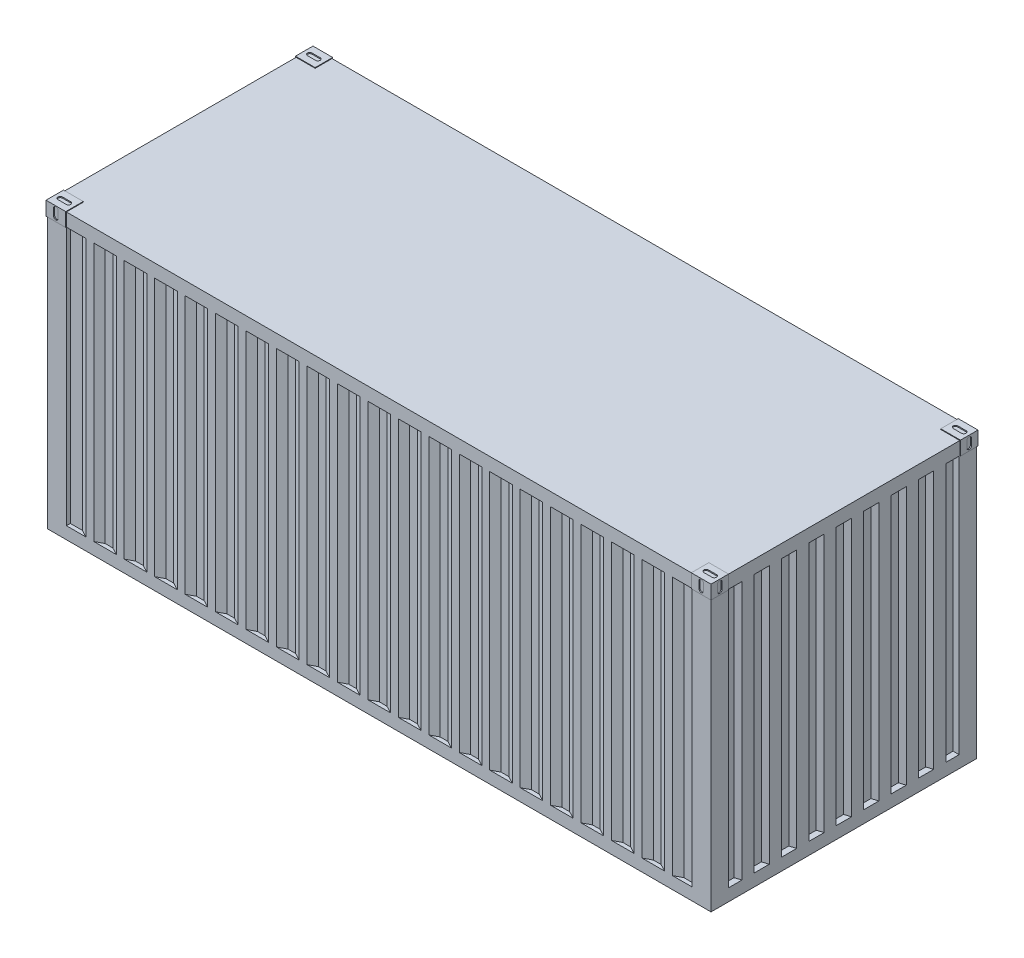
SolidWorks part; units mm, degrees
ref_plane "Front Plane" through (0, 0, 0) normal (0, 0, 1) x (1, 0, 0)
ref_plane "Top Plane" through (0, 0, 0) normal (0, 1, 0) x (1, 0, 0)
ref_plane "Right Plane" through (0, 0, 0) normal (1, 0, 0) x (0, 0, -1)
sketch "Sketch1" plane through (0, 0, 0) normal (0, 1, 0) x (1, 0, 0)
  line L1 (0, 0) -> (6058, 0)
  line L2 (0, 0) -> (0, 2424.7)
  line L3 (0, 2424.7) -> (6058, 2424.7)
  line L4 (6058, 0) -> (6058, 2424.7)
  dimension "D1" = 6058
  dimension "D2" = 2424.7
extrude "Boss-Extrude1" add sketch "Sketch1" along normal blind 2591
ref_plane "Plane-Mid-Length" through (0, 0, -1212.35) normal (0, 0, 1) x (1, 0, 0)
ref_plane "Plane-Mid-Width" through (3029, 0, 0) normal (-1, 0, 0) x (0, 0, 1)
ref_plane "Plane-Mid-Height" through (0, 1295.5, 0) normal (0, 1, 0) x (1, 0, 0)
ref_plane "Top of Corrugation" through (0, 2471, 0) normal (0, 1, 0) x (1, 0, 0)
ref_plane "Floor/Bottom of Corrugation" through (0, 111, 0) normal (0, 1, 0) x (1, 0, 0)
sketch "Sketch4" plane through (0, 2591, 0) normal (0, 1, 0) x (1, 0, 0)
  line L0 (6058, 2424.7) -> (5884, 2424.7)
  line L1 (6058, 2424.7) -> (0, 2424.7) construction
  line L2 (5884, 2424.7) -> (5884, 2388.7)
  line L3 (5884, 2388.7) -> (5774, 2388.7)
  line L4 (5774, 2388.7) -> (5706, 2424.7)
  line L5 (5706, 2424.7) -> (5634, 2424.7)
  line L6 (5634, 2424.7) -> (5566, 2388.7)
  line L7 (5566, 2388.7) -> (5496, 2388.7)
  line L8 (5496, 2388.7) -> (5428, 2424.7)
  line L9 (5428, 2424.7) -> (5356, 2424.7)
  line L10 (5356, 2424.7) -> (5288, 2388.7)
  line L11 (5288, 2388.7) -> (5218, 2388.7)
  line L12 (5218, 2388.7) -> (5150, 2424.7)
  line L13 (5150, 2424.7) -> (5078, 2424.7)
  line L14 (5078, 2424.7) -> (5010, 2388.7)
  line L15 (5010, 2388.7) -> (4940, 2388.7)
  line L16 (4940, 2388.7) -> (4872, 2424.7)
  line L17 (4872, 2424.7) -> (4800, 2424.7)
  line L18 (4800, 2424.7) -> (4732, 2388.7)
  line L19 (4732, 2388.7) -> (4662, 2388.7)
  line L20 (4662, 2388.7) -> (4594, 2424.7)
  line L21 (4594, 2424.7) -> (4522, 2424.7)
  line L22 (4522, 2424.7) -> (4454, 2388.7)
  line L23 (4454, 2388.7) -> (4384, 2388.7)
  line L24 (4384, 2388.7) -> (4316, 2424.7)
  line L25 (4316, 2424.7) -> (4244, 2424.7)
  line L26 (4244, 2424.7) -> (4176, 2388.7)
  line L27 (4176, 2388.7) -> (4106, 2388.7)
  line L28 (4106, 2388.7) -> (4038, 2424.7)
  line L29 (4038, 2424.7) -> (3966, 2424.7)
  line L30 (3966, 2424.7) -> (3898, 2388.7)
  line L31 (3898, 2388.7) -> (3828, 2388.7)
  line L32 (3828, 2388.7) -> (3760, 2424.7)
  line L33 (3760, 2424.7) -> (3688, 2424.7)
  line L34 (3688, 2424.7) -> (3620, 2388.7)
  line L35 (3620, 2388.7) -> (3550, 2388.7)
  line L36 (3550, 2388.7) -> (3482, 2424.7)
  line L37 (3482, 2424.7) -> (3410, 2424.7)
  line L38 (3410, 2424.7) -> (3342, 2388.7)
  line L39 (3342, 2388.7) -> (3272, 2388.7)
  line L40 (3272, 2388.7) -> (3204, 2424.7)
  line L41 (3204, 2424.7) -> (3132, 2424.7)
  line L42 (3132, 2424.7) -> (3064, 2388.7)
  line L43 (3064, 2388.7) -> (2994, 2388.7)
  line L44 (2994, 2388.7) -> (2926, 2424.7)
  line L45 (2926, 2424.7) -> (2854, 2424.7)
  line L46 (2854, 2424.7) -> (2786, 2388.7)
  line L47 (2786, 2388.7) -> (2716, 2388.7)
  line L48 (2716, 2388.7) -> (2648, 2424.7)
  line L49 (2648, 2424.7) -> (2576, 2424.7)
  line L50 (2576, 2424.7) -> (2508, 2388.7)
  line L51 (2508, 2388.7) -> (2438, 2388.7)
  line L52 (2438, 2388.7) -> (2370, 2424.7)
  line L53 (2370, 2424.7) -> (2298, 2424.7)
  line L54 (2298, 2424.7) -> (2230, 2388.7)
  line L55 (2230, 2388.7) -> (2160, 2388.7)
  line L56 (2160, 2388.7) -> (2092, 2424.7)
  line L57 (2092, 2424.7) -> (2020, 2424.7)
  line L58 (2020, 2424.7) -> (1952, 2388.7)
  line L59 (1952, 2388.7) -> (1882, 2388.7)
  line L60 (1882, 2388.7) -> (1814, 2424.7)
  line L61 (1814, 2424.7) -> (1742, 2424.7)
  line L62 (1742, 2424.7) -> (1674, 2388.7)
  line L63 (1674, 2388.7) -> (1604, 2388.7)
  line L64 (1604, 2388.7) -> (1536, 2424.7)
  line L65 (1536, 2424.7) -> (1464, 2424.7)
  line L66 (1464, 2424.7) -> (1396, 2388.7)
  line L67 (1396, 2388.7) -> (1326, 2388.7)
  line L68 (1326, 2388.7) -> (1258, 2424.7)
  line L69 (1258, 2424.7) -> (1186, 2424.7)
  line L70 (1186, 2424.7) -> (1118, 2388.7)
  line L71 (1118, 2388.7) -> (1048, 2388.7)
  line L72 (1048, 2388.7) -> (980, 2424.7)
  line L73 (980, 2424.7) -> (908, 2424.7)
  line L74 (908, 2424.7) -> (840, 2388.7)
  line L75 (840, 2388.7) -> (770, 2388.7)
  line L76 (770, 2388.7) -> (702, 2424.7)
  line L77 (702, 2424.7) -> (630, 2424.7)
  line L78 (630, 2424.7) -> (562, 2388.7)
  line L79 (562, 2388.7) -> (492, 2388.7)
  line L80 (492, 2388.7) -> (424, 2424.7)
  line L81 (0, 2424.7) -> (174, 2424.7)
  line L82 (174, 2424.7) -> (174, 2388.7)
  line L83 (174, 2388.7) -> (284, 2388.7)
  line L84 (284, 2388.7) -> (352, 2424.7)
  line L85 (352, 2424.7) -> (424, 2424.7)
  line L86 (-1425.05, 1212.35) -> (1425.05, 1212.35) construction
  line L87 (352, 0) -> (424, 0)
  line L88 (284, 36) -> (352, 0)
  line L89 (174, 36) -> (284, 36)
  line L90 (174, 0) -> (174, 36)
  line L91 (0, 0) -> (174, 0)
  line L92 (492, 36) -> (424, 0)
  line L93 (562, 36) -> (492, 36)
  line L94 (630, 0) -> (562, 36)
  line L95 (702, 0) -> (630, 0)
  line L96 (770, 36) -> (702, 0)
  line L97 (840, 36) -> (770, 36)
  line L98 (908, 0) -> (840, 36)
  line L99 (980, 0) -> (908, 0)
  line L100 (1048, 36) -> (980, 0)
  line L101 (1118, 36) -> (1048, 36)
  line L102 (1186, 0) -> (1118, 36)
  line L103 (1258, 0) -> (1186, 0)
  line L104 (1326, 36) -> (1258, 0)
  line L105 (1396, 36) -> (1326, 36)
  line L106 (1464, 0) -> (1396, 36)
  line L107 (1536, 0) -> (1464, 0)
  line L108 (1604, 36) -> (1536, 0)
  line L109 (1674, 36) -> (1604, 36)
  line L110 (1742, 0) -> (1674, 36)
  line L111 (1814, 0) -> (1742, 0)
  line L112 (1882, 36) -> (1814, 0)
  line L113 (1952, 36) -> (1882, 36)
  line L114 (2020, 0) -> (1952, 36)
  line L115 (2092, 0) -> (2020, 0)
  line L116 (2160, 36) -> (2092, 0)
  line L117 (2230, 36) -> (2160, 36)
  line L118 (2298, 0) -> (2230, 36)
  line L119 (2370, 0) -> (2298, 0)
  line L120 (2438, 36) -> (2370, 0)
  line L121 (2508, 36) -> (2438, 36)
  line L122 (2576, 0) -> (2508, 36)
  line L123 (2648, 0) -> (2576, 0)
  line L124 (2716, 36) -> (2648, 0)
  line L125 (2786, 36) -> (2716, 36)
  line L126 (2854, 0) -> (2786, 36)
  line L127 (2926, 0) -> (2854, 0)
  line L128 (2994, 36) -> (2926, 0)
  line L129 (3064, 36) -> (2994, 36)
  line L130 (3132, 0) -> (3064, 36)
  line L131 (3204, 0) -> (3132, 0)
  line L132 (3272, 36) -> (3204, 0)
  line L133 (3342, 36) -> (3272, 36)
  line L134 (3410, 0) -> (3342, 36)
  line L135 (3482, 0) -> (3410, 0)
  line L136 (3550, 36) -> (3482, 0)
  line L137 (3620, 36) -> (3550, 36)
  line L138 (3688, 0) -> (3620, 36)
  line L139 (3760, 0) -> (3688, 0)
  line L140 (3828, 36) -> (3760, 0)
  line L141 (3898, 36) -> (3828, 36)
  line L142 (3966, 0) -> (3898, 36)
  line L143 (4038, 0) -> (3966, 0)
  line L144 (4106, 36) -> (4038, 0)
  line L145 (4176, 36) -> (4106, 36)
  line L146 (4244, 0) -> (4176, 36)
  line L147 (4316, 0) -> (4244, 0)
  line L148 (4384, 36) -> (4316, 0)
  line L149 (4454, 36) -> (4384, 36)
  line L150 (4522, 0) -> (4454, 36)
  line L151 (4594, 0) -> (4522, 0)
  line L152 (4662, 36) -> (4594, 0)
  line L153 (4732, 36) -> (4662, 36)
  line L154 (4800, 0) -> (4732, 36)
  line L155 (4872, 0) -> (4800, 0)
  line L156 (4940, 36) -> (4872, 0)
  line L157 (5010, 36) -> (4940, 36)
  line L158 (5078, 0) -> (5010, 36)
  line L159 (5150, 0) -> (5078, 0)
  line L160 (5218, 36) -> (5150, 0)
  line L161 (5288, 36) -> (5218, 36)
  line L162 (5356, 0) -> (5288, 36)
  line L163 (5428, 0) -> (5356, 0)
  line L164 (5496, 36) -> (5428, 0)
  line L165 (5566, 36) -> (5496, 36)
  line L166 (5634, 0) -> (5566, 36)
  line L167 (5706, 0) -> (5634, 0)
  line L168 (5774, 36) -> (5706, 0)
  line L169 (5884, 36) -> (5774, 36)
  line L170 (5884, 0) -> (5884, 36)
  line L171 (6058, 0) -> (5884, 0)
  line L172 (6058, 2424.7) -> (6058, 2264.7)
  line L173 (6058, 0) -> (6058, 2424.7) construction
  line L174 (6058, 2264.7) -> (6003, 2264.7)
  line L175 (6003, 2264.7) -> (6003, 2160.35)
  line L176 (6003, 2160.35) -> (6058, 2142.35)
  line L177 (6058, 2142.35) -> (6058, 2032.35)
  line L178 (6058, 2032.35) -> (6003, 2014.35)
  line L179 (6003, 2014.35) -> (6003, 1910.35)
  line L180 (6003, 1910.35) -> (6058, 1892.35)
  line L181 (6058, 1892.35) -> (6058, 1782.35)
  line L182 (6058, 1782.35) -> (6003, 1764.35)
  line L183 (6003, 1764.35) -> (6003, 1660.35)
  line L184 (6003, 1660.35) -> (6058, 1642.35)
  line L185 (6058, 1642.35) -> (6058, 1532.35)
  line L186 (6058, 1532.35) -> (6003, 1514.35)
  line L187 (6003, 1514.35) -> (6003, 1410.35)
  line L188 (6003, 1410.35) -> (6058, 1392.35)
  line L189 (6058, 1392.35) -> (6058, 1282.35)
  line L190 (6058, 1282.35) -> (6003, 1264.35)
  line L191 (6003, 1264.35) -> (6003, 1160.35)
  line L192 (6003, 1160.35) -> (6058, 1142.35)
  line L193 (6058, 1142.35) -> (6058, 1032.35)
  line L194 (6058, 1032.35) -> (6003, 1014.35)
  line L195 (6003, 1014.35) -> (6003, 910.35)
  line L196 (6003, 910.35) -> (6058, 892.35)
  line L197 (6058, 892.35) -> (6058, 782.35)
  line L198 (6058, 782.35) -> (6003, 764.35)
  line L199 (6003, 764.35) -> (6003, 660.35)
  line L200 (6003, 660.35) -> (6058, 642.35)
  line L201 (6058, 642.35) -> (6058, 532.35)
  line L202 (6058, 532.35) -> (6003, 514.35)
  line L203 (6003, 514.35) -> (6003, 410.35)
  line L204 (6058, 0) -> (6058, 160)
  line L205 (6058, 160) -> (6003, 160)
  line L206 (6003, 160) -> (6003, 264.35)
  line L207 (6003, 264.35) -> (6058, 282.35)
  line L208 (6058, 282.35) -> (6058, 392.35)
  line L209 (6058, 392.35) -> (6003, 410.35)
  line L210 (0, 2424.7) -> (-440.0749, 2424.7)
  line L211 (-440.0749, 2424.7) -> (-440.0749, 3030.4857)
  line L212 (-440.0749, 3030.4857) -> (7385.1907, 3030.4857)
  line L213 (7385.1907, 3030.4857) -> (7385.1907, -895.4636)
  line L214 (7385.1907, -895.4636) -> (-1155.3936, -895.4636)
  line L215 (-1155.3936, -895.4636) -> (-1155.3936, 0)
  line L216 (-1155.3936, 0) -> (0, 0)
  dimension "D1" = 174
  dimension "D2" = 36
  dimension "D3" = 36
  dimension "D4" = 72
  dimension "D5" = 68
  dimension "D6" = 68
  dimension "D7" = 70
  dimension "D8" = 68
  dimension "D9" = 110
  dimension "D11" = 174
  dimension "D12" = 72
  dimension "D13" = 68
  dimension "D14" = 160
  dimension "D15" = 160
  dimension "D16" = 55
  dimension "D17" = 104.35
  dimension "D18" = 18
  dimension "D19" = 18
  dimension "D20" = 110
  dimension "D21" = 104
  dimension "D23" = 18
  dimension "D24" = 18
  dimension "D25" = 110
  dimension "D10" = 19
  dimension "D22" = 7
extrude "Cut-Extrude1" cut sketch "Sketch4" against normal up to surface (2480 mm away) from surface up to plane "Floor/Bottom of Corrugation" starting at plane "Top of Corrugation"
sketch "Sketch5" plane through (0, 1295.5, 0) normal (0, 1, 0) x (1, 0, 0)
  line L0 (0, 2423.1) -> (172.4, 2423.1)
  line L1 (0, 2424.7) -> (0, 0) construction
  line L2 (172.4, 2423.1) -> (172.4, 2387.1)
  line L3 (172.4, 2387.1) -> (284.3974, 2387.1)
  line L4 (284.3974, 2387.1) -> (352.3974, 2423.1)
  line L5 (352.3974, 2423.1) -> (423.6026, 2423.1)
  line L6 (423.6026, 2423.1) -> (491.6026, 2387.1)
  line L7 (491.6026, 2387.1) -> (562.3974, 2387.1)
  line L8 (562.3974, 2387.1) -> (630.3974, 2423.1)
  line L9 (6058, 2424.7) -> (0, 2424.7) construction
  line L10 (174, 2388.7) -> (174, 2424.7) construction
  line L11 (284, 2388.7) -> (174, 2388.7) construction
  line L12 (352, 2424.7) -> (284, 2388.7) construction
  line L13 (492, 2388.7) -> (424, 2424.7) construction
  line L14 (562, 2388.7) -> (492, 2388.7) construction
  line L15 (630, 2424.7) -> (562, 2388.7) construction
  line L16 (630.3974, 2423.1) -> (701.6026, 2423.1)
  line L17 (701.6026, 2423.1) -> (769.6026, 2387.1)
  line L18 (769.6026, 2387.1) -> (840.3974, 2387.1)
  line L19 (840.3974, 2387.1) -> (908.3974, 2423.1)
  line L20 (908.3974, 2423.1) -> (979.6026, 2423.1)
  line L21 (979.6026, 2423.1) -> (1047.6026, 2387.1)
  line L22 (1047.6026, 2387.1) -> (1118.3974, 2387.1)
  line L23 (1118.3974, 2387.1) -> (1186.3974, 2423.1)
  line L24 (1186.3974, 2423.1) -> (1257.6026, 2423.1)
  line L25 (1257.6026, 2423.1) -> (1325.6026, 2387.1)
  line L26 (1325.6026, 2387.1) -> (1396.3974, 2387.1)
  line L27 (1396.3974, 2387.1) -> (1464.3974, 2423.1)
  line L28 (1464.3974, 2423.1) -> (1535.6026, 2423.1)
  line L29 (1535.6026, 2423.1) -> (1603.6026, 2387.1)
  line L30 (1603.6026, 2387.1) -> (1674.3974, 2387.1)
  line L31 (1674.3974, 2387.1) -> (1742.3974, 2423.1)
  line L32 (1742.3974, 2423.1) -> (1813.6026, 2423.1)
  line L33 (1813.6026, 2423.1) -> (1881.6026, 2387.1)
  line L34 (1881.6026, 2387.1) -> (1952.3974, 2387.1)
  line L35 (1952.3974, 2387.1) -> (2020.3974, 2423.1)
  line L36 (2020.3974, 2423.1) -> (2091.6026, 2423.1)
  line L37 (2091.6026, 2423.1) -> (2159.6026, 2387.1)
  line L38 (2159.6026, 2387.1) -> (2230.3974, 2387.1)
  line L39 (2230.3974, 2387.1) -> (2298.3974, 2423.1)
  line L40 (2298.3974, 2423.1) -> (2369.6026, 2423.1)
  line L41 (2369.6026, 2423.1) -> (2437.6026, 2387.1)
  line L42 (2437.6026, 2387.1) -> (2508.3974, 2387.1)
  line L43 (2508.3974, 2387.1) -> (2576.3974, 2423.1)
  line L44 (2576.3974, 2423.1) -> (2647.6026, 2423.1)
  line L45 (2647.6026, 2423.1) -> (2715.6026, 2387.1)
  line L46 (2715.6026, 2387.1) -> (2786.3974, 2387.1)
  line L47 (2786.3974, 2387.1) -> (2854.3974, 2423.1)
  line L48 (2854.3974, 2423.1) -> (2925.6026, 2423.1)
  line L49 (2925.6026, 2423.1) -> (2993.6026, 2387.1)
  line L50 (2993.6026, 2387.1) -> (3064.3974, 2387.1)
  line L51 (3064.3974, 2387.1) -> (3132.3974, 2423.1)
  line L52 (3132.3974, 2423.1) -> (3203.6026, 2423.1)
  line L53 (3203.6026, 2423.1) -> (3271.6026, 2387.1)
  line L54 (3271.6026, 2387.1) -> (3342.3974, 2387.1)
  line L55 (3342.3974, 2387.1) -> (3410.3974, 2423.1)
  line L56 (3410.3974, 2423.1) -> (3481.6026, 2423.1)
  line L57 (3481.6026, 2423.1) -> (3549.6026, 2387.1)
  line L58 (3549.6026, 2387.1) -> (3620.3974, 2387.1)
  line L59 (3620.3974, 2387.1) -> (3688.3974, 2423.1)
  line L60 (3688.3974, 2423.1) -> (3759.6026, 2423.1)
  line L61 (3759.6026, 2423.1) -> (3827.6026, 2387.1)
  line L62 (3827.6026, 2387.1) -> (3898.3974, 2387.1)
  line L63 (3898.3974, 2387.1) -> (3966.3974, 2423.1)
  line L64 (3966.3974, 2423.1) -> (4037.6026, 2423.1)
  line L65 (4037.6026, 2423.1) -> (4105.6026, 2387.1)
  line L66 (4105.6026, 2387.1) -> (4176.3974, 2387.1)
  line L67 (4176.3974, 2387.1) -> (4244.3974, 2423.1)
  line L68 (4244.3974, 2423.1) -> (4315.6026, 2423.1)
  line L69 (4315.6026, 2423.1) -> (4383.6026, 2387.1)
  line L70 (4383.6026, 2387.1) -> (4454.3974, 2387.1)
  line L71 (4454.3974, 2387.1) -> (4522.3974, 2423.1)
  line L72 (4522.3974, 2423.1) -> (4593.6026, 2423.1)
  line L73 (4593.6026, 2423.1) -> (4661.6026, 2387.1)
  line L74 (4661.6026, 2387.1) -> (4732.3974, 2387.1)
  line L75 (4732.3974, 2387.1) -> (4800.3974, 2423.1)
  line L76 (4800.3974, 2423.1) -> (4871.6026, 2423.1)
  line L77 (4871.6026, 2423.1) -> (4939.6026, 2387.1)
  line L78 (4939.6026, 2387.1) -> (5010.3974, 2387.1)
  line L79 (5010.3974, 2387.1) -> (5078.3974, 2423.1)
  line L80 (5078.3974, 2423.1) -> (5149.6026, 2423.1)
  line L81 (5149.6026, 2423.1) -> (5217.6026, 2387.1)
  line L82 (5217.6026, 2387.1) -> (5288.3974, 2387.1)
  line L83 (5288.3974, 2387.1) -> (5356.3974, 2423.1)
  line L84 (5356.3974, 2423.1) -> (5427.6026, 2423.1)
  line L85 (5427.6026, 2423.1) -> (5495.6026, 2387.1)
  line L86 (5495.6026, 2387.1) -> (5566.3974, 2387.1)
  line L87 (5566.3974, 2387.1) -> (5634.3974, 2423.1)
  line L88 (5634.3974, 2423.1) -> (5705.6026, 2423.1)
  line L89 (5705.6026, 2423.1) -> (5773.6026, 2387.1)
  line L90 (5773.6026, 2387.1) -> (5885.6, 2387.1)
  line L91 (5885.6, 2387.1) -> (5885.6, 2423.1)
  line L92 (5885.6, 2423.1) -> (6056.4, 2423.1)
  line L93 (5774, 2388.7) -> (5706, 2424.7) construction
  line L94 (5884, 2388.7) -> (5774, 2388.7) construction
  line L95 (5884, 2424.7) -> (5884, 2388.7) construction
  line L96 (6058, 0) -> (6058, 2424.7) construction
  line L97 (-1425.05, 1212.35) -> (1425.05, 1212.35) construction
  line L98 (5885.6, 1.6) -> (6056.4, 1.6)
  line L99 (5885.6, 37.6) -> (5885.6, 1.6)
  line L100 (5773.6026, 37.6) -> (5885.6, 37.6)
  line L101 (5705.6026, 1.6) -> (5773.6026, 37.6)
  line L102 (5634.3974, 1.6) -> (5705.6026, 1.6)
  line L103 (5566.3974, 37.6) -> (5634.3974, 1.6)
  line L104 (5495.6026, 37.6) -> (5566.3974, 37.6)
  line L105 (5427.6026, 1.6) -> (5495.6026, 37.6)
  line L106 (5356.3974, 1.6) -> (5427.6026, 1.6)
  line L107 (5288.3974, 37.6) -> (5356.3974, 1.6)
  line L108 (5217.6026, 37.6) -> (5288.3974, 37.6)
  line L109 (5149.6026, 1.6) -> (5217.6026, 37.6)
  line L110 (5078.3974, 1.6) -> (5149.6026, 1.6)
  line L111 (5010.3974, 37.6) -> (5078.3974, 1.6)
  line L112 (4939.6026, 37.6) -> (5010.3974, 37.6)
  line L113 (4871.6026, 1.6) -> (4939.6026, 37.6)
  line L114 (4800.3974, 1.6) -> (4871.6026, 1.6)
  line L115 (4732.3974, 37.6) -> (4800.3974, 1.6)
  line L116 (4661.6026, 37.6) -> (4732.3974, 37.6)
  line L117 (4593.6026, 1.6) -> (4661.6026, 37.6)
  line L118 (4522.3974, 1.6) -> (4593.6026, 1.6)
  line L119 (4454.3974, 37.6) -> (4522.3974, 1.6)
  line L120 (4383.6026, 37.6) -> (4454.3974, 37.6)
  line L121 (4315.6026, 1.6) -> (4383.6026, 37.6)
  line L122 (4244.3974, 1.6) -> (4315.6026, 1.6)
  line L123 (4176.3974, 37.6) -> (4244.3974, 1.6)
  line L124 (4105.6026, 37.6) -> (4176.3974, 37.6)
  line L125 (4037.6026, 1.6) -> (4105.6026, 37.6)
  line L126 (3966.3974, 1.6) -> (4037.6026, 1.6)
  line L127 (3898.3974, 37.6) -> (3966.3974, 1.6)
  line L128 (3827.6026, 37.6) -> (3898.3974, 37.6)
  line L129 (3759.6026, 1.6) -> (3827.6026, 37.6)
  line L130 (3688.3974, 1.6) -> (3759.6026, 1.6)
  line L131 (3620.3974, 37.6) -> (3688.3974, 1.6)
  line L132 (3549.6026, 37.6) -> (3620.3974, 37.6)
  line L133 (3481.6026, 1.6) -> (3549.6026, 37.6)
  line L134 (3410.3974, 1.6) -> (3481.6026, 1.6)
  line L135 (3342.3974, 37.6) -> (3410.3974, 1.6)
  line L136 (3271.6026, 37.6) -> (3342.3974, 37.6)
  line L137 (3203.6026, 1.6) -> (3271.6026, 37.6)
  line L138 (3132.3974, 1.6) -> (3203.6026, 1.6)
  line L139 (3064.3974, 37.6) -> (3132.3974, 1.6)
  line L140 (2993.6026, 37.6) -> (3064.3974, 37.6)
  line L141 (2925.6026, 1.6) -> (2993.6026, 37.6)
  line L142 (2854.3974, 1.6) -> (2925.6026, 1.6)
  line L143 (2786.3974, 37.6) -> (2854.3974, 1.6)
  line L144 (2715.6026, 37.6) -> (2786.3974, 37.6)
  line L145 (2647.6026, 1.6) -> (2715.6026, 37.6)
  line L146 (2576.3974, 1.6) -> (2647.6026, 1.6)
  line L147 (2508.3974, 37.6) -> (2576.3974, 1.6)
  line L148 (2437.6026, 37.6) -> (2508.3974, 37.6)
  line L149 (2369.6026, 1.6) -> (2437.6026, 37.6)
  line L150 (2298.3974, 1.6) -> (2369.6026, 1.6)
  line L151 (2230.3974, 37.6) -> (2298.3974, 1.6)
  line L152 (2159.6026, 37.6) -> (2230.3974, 37.6)
  line L153 (2091.6026, 1.6) -> (2159.6026, 37.6)
  line L154 (2020.3974, 1.6) -> (2091.6026, 1.6)
  line L155 (1952.3974, 37.6) -> (2020.3974, 1.6)
  line L156 (1881.6026, 37.6) -> (1952.3974, 37.6)
  line L157 (1813.6026, 1.6) -> (1881.6026, 37.6)
  line L158 (1742.3974, 1.6) -> (1813.6026, 1.6)
  line L159 (1674.3974, 37.6) -> (1742.3974, 1.6)
  line L160 (1603.6026, 37.6) -> (1674.3974, 37.6)
  line L161 (1535.6026, 1.6) -> (1603.6026, 37.6)
  line L162 (1464.3974, 1.6) -> (1535.6026, 1.6)
  line L163 (1396.3974, 37.6) -> (1464.3974, 1.6)
  line L164 (1325.6026, 37.6) -> (1396.3974, 37.6)
  line L165 (1257.6026, 1.6) -> (1325.6026, 37.6)
  line L166 (1186.3974, 1.6) -> (1257.6026, 1.6)
  line L167 (1118.3974, 37.6) -> (1186.3974, 1.6)
  line L168 (1047.6026, 37.6) -> (1118.3974, 37.6)
  line L169 (979.6026, 1.6) -> (1047.6026, 37.6)
  line L170 (908.3974, 1.6) -> (979.6026, 1.6)
  line L171 (840.3974, 37.6) -> (908.3974, 1.6)
  line L172 (769.6026, 37.6) -> (840.3974, 37.6)
  line L173 (701.6026, 1.6) -> (769.6026, 37.6)
  line L174 (630.3974, 1.6) -> (701.6026, 1.6)
  line L175 (562.3974, 37.6) -> (630.3974, 1.6)
  line L176 (491.6026, 37.6) -> (562.3974, 37.6)
  line L177 (423.6026, 1.6) -> (491.6026, 37.6)
  line L178 (352.3974, 1.6) -> (423.6026, 1.6)
  line L179 (284.3974, 37.6) -> (352.3974, 1.6)
  line L180 (172.4, 37.6) -> (284.3974, 37.6)
  line L181 (172.4, 1.6) -> (172.4, 37.6)
  line L182 (0, 1.6) -> (172.4, 1.6)
  line L183 (6056.4, 2423.1) -> (6056.4, 2266.3)
  line L184 (6056.4, 2266.3) -> (6001.4, 2266.3)
  line L185 (6003, 2264.7) -> (6058, 2264.7) construction
  line L186 (6001.4, 2266.3) -> (6001.4, 2159.1901)
  line L187 (6001.4, 2159.1901) -> (6056.4, 2141.1901)
  line L188 (6056.4, 2141.1901) -> (6056.4, 2033.5099)
  line L189 (6056.4, 2033.5099) -> (6001.4, 2015.5099)
  line L190 (6001.4, 2015.5099) -> (6001.4, 1909.1901)
  line L191 (6001.4, 1909.1901) -> (6056.4, 1891.1901)
  line L192 (6058, 2142.35) -> (6003, 2160.35) construction
  line L193 (6003, 2160.35) -> (6003, 2264.7) construction
  line L194 (6003, 2014.35) -> (6058, 2032.35) construction
  line L195 (6003, 1910.35) -> (6003, 2014.35) construction
  line L196 (6058, 1892.35) -> (6003, 1910.35) construction
  line L197 (6056.4, 1891.1901) -> (6056.4, 1783.5099)
  line L198 (6056.4, 1783.5099) -> (6001.4, 1765.5099)
  line L199 (6001.4, 1765.5099) -> (6001.4, 1659.1901)
  line L200 (6001.4, 1659.1901) -> (6056.4, 1641.1901)
  line L201 (6056.4, 1641.1901) -> (6056.4, 1533.5099)
  line L202 (6056.4, 1533.5099) -> (6001.4, 1515.5099)
  line L203 (6001.4, 1515.5099) -> (6001.4, 1409.1901)
  line L204 (6001.4, 1409.1901) -> (6056.4, 1391.1901)
  line L205 (6056.4, 1391.1901) -> (6056.4, 1283.5099)
  line L206 (6056.4, 1283.5099) -> (6001.4, 1265.5099)
  line L207 (6001.4, 1265.5099) -> (6001.4, 1159.1901)
  line L208 (6001.4, 1159.1901) -> (6056.4, 1141.1901)
  line L209 (6056.4, 1141.1901) -> (6056.4, 1033.5099)
  line L210 (6056.4, 1033.5099) -> (6001.4, 1015.5099)
  line L211 (6001.4, 1015.5099) -> (6001.4, 909.1901)
  line L212 (6001.4, 909.1901) -> (6056.4, 891.1901)
  line L213 (6056.4, 891.1901) -> (6056.4, 783.5099)
  line L214 (6056.4, 783.5099) -> (6001.4, 765.5099)
  line L215 (6001.4, 765.5099) -> (6001.4, 659.1901)
  line L216 (6001.4, 659.1901) -> (6056.4, 641.1901)
  line L217 (6056.4, 641.1901) -> (6056.4, 533.5099)
  line L218 (6056.4, 533.5099) -> (6001.4, 515.5099)
  line L219 (6001.4, 515.5099) -> (6001.4, 409.1901)
  line L220 (6001.4, 409.1901) -> (6056.4, 391.1901)
  line L221 (6056.4, 391.1901) -> (6056.4, 283.5099)
  line L222 (6056.4, 283.5099) -> (6001.4, 265.5099)
  line L223 (6001.4, 265.5099) -> (6001.4, 158.4)
  line L224 (6001.4, 158.4) -> (6056.4, 158.4)
  line L225 (6056.4, 158.4) -> (6056.4, 1.6)
  line L226 (6003, 264.35) -> (6058, 282.35) construction
  line L227 (6003, 160) -> (6003, 264.35) construction
  line L228 (6058, 160) -> (6003, 160) construction
  line L229 (0, 2423.1) -> (0, 1.6)
  dimension "D1" = 1.6
  dimension "D2" = 1.6
  dimension "D3" = 1.6
  dimension "D4" = 1.6
  dimension "D5" = 1.6
  dimension "D6" = 1.6
  dimension "D7" = 1.6
  dimension "D8" = 1.6
  dimension "D9" = 1.6
  dimension "D10" = 19
  dimension "D11" = 1.6
  dimension "D12" = 1.6
  dimension "D13" = 1.6
  dimension "D14" = 1.6
  dimension "D15" = 1.6
  dimension "D16" = 1.6
  dimension "D17" = 1.6
  dimension "D18" = 1.6
  dimension "D19" = 1.6
  dimension "D20" = 1.6
  dimension "D21" = 1.6
  dimension "D24" = 1.6
  dimension "D25" = 1.6
  dimension "D26" = 1.6
  dimension "D23" = 7
extrude "Cut-Extrude2" cut sketch "Sketch5" against normal up to surface (1184.5 mm away) and the other way up to surface (1175.5 mm away) up to plane "Floor/Bottom of Corrugation" other way up to plane "Top of Corrugation"
ref_plane "Back Wall" through (6001.4, 0, 0) normal (-1, 0, 0) x (0, 0, 1)
ref_plane "Side Wall" through (0, 0, -37.6) normal (0, 0, -1) x (-1, 0, 0)
sketch "Sketch6" plane through (0, 2591, 0) normal (0, 1, 0) x (1, 0, 0)
  line L0 (6058, 0) -> (6058, 2424.7) construction
  line L1 (5884, 154) -> (6064, 154)
  line L2 (5884, 154) -> (5884, -6)
  line L3 (5884, -6) -> (6064, -6)
  line L4 (6064, 154) -> (6064, -6)
  line L5 (0, 0) -> (6058, 0) construction
  dimension "D1" = 6
  dimension "D2" = 6
  dimension "D3" = 180
  dimension "D4" = 160
extrude "Corner Support" add sketch "Sketch6" along normal blind 6 and the other way up to surface (120 mm away) other way up to plane "Top of Corrugation"
sketch "Sketch7" plane through (0, 0, 6) normal (0, 0, 1) x (1, 0, 0)
  line L0 (5953, 2569) -> (5953, 2506.6)
  line L1 (5995, 2569) -> (5995, 2506.6)
  line L3 (6064, 2471) -> (6064, 2597) construction
  line L4 (5884, 2597) -> (6064, 2597) construction
  arc A0 (5953, 2506.6) -> (5995, 2506.6) centre (5974, 2506.6) ccw
  arc A1 (5953, 2569) -> (5995, 2569) centre (5974, 2569) cw
  point P8 (0, 0)
  point P10 (5972.1603, 2560.8053)
  dimension "D1" = 42
  dimension "D2" = 90
  dimension "D3" = 28
extrude "Cut-Extrude3" cut sketch "Sketch7" against normal blind 10
sketch "Sketch8" plane through (6064, 0, 0) normal (1, 0, 0) x (0, 0, -1)
  line L0 (53, 2564.1204) -> (53, 2504.1204)
  line L1 (95, 2504.1204) -> (95, 2564.1204)
  line L4 (-6, 2471) -> (-6, 2597) construction
  arc A0 (53, 2504.1204) -> (95, 2504.1204) centre (74, 2504.1204) ccw
  arc A1 (95, 2564.1204) -> (53, 2564.1204) centre (74, 2564.1204) ccw
  dimension "D2" = 42
  dimension "D1" = 80
  dimension "D3" = 60
sketch "Sketch9" plane through (0, 2597, 0) normal (0, 1, 0) x (1, 0, 0)
  line L0 (5939, 95) -> (6014, 95)
  line L1 (6014, 53) -> (5939, 53)
  line L2 (5884, 154) -> (6058, 154) construction
  line L3 (5884, 154) -> (5884, -6) construction
  arc A0 (6014, 95) -> (6014, 53) centre (6014, 74) cw
  arc A1 (5939, 53) -> (5939, 95) centre (5939, 74) cw
  dimension "D1" = 42
  dimension "D2" = 75
  dimension "D3" = 80
  dimension "D4" = 55
extrude "Cut-Extrude4" cut sketch "Sketch9" against normal blind 10
extrude "Cut-Extrude5" cut sketch "Sketch8" against normal blind 10
mirror "Mirror1" about plane through (3029, 0, 0) normal (-1, 0, 0) of "Cut-Extrude4", "Cut-Extrude3", "Corner Support", "Cut-Extrude5"
mirror "Mirror2" about plane through (0, 0, -1212.35) normal (0, 0, 1) of "Cut-Extrude3", "Cut-Extrude4", "Cut-Extrude5", "Mirror1", "Corner Support"
